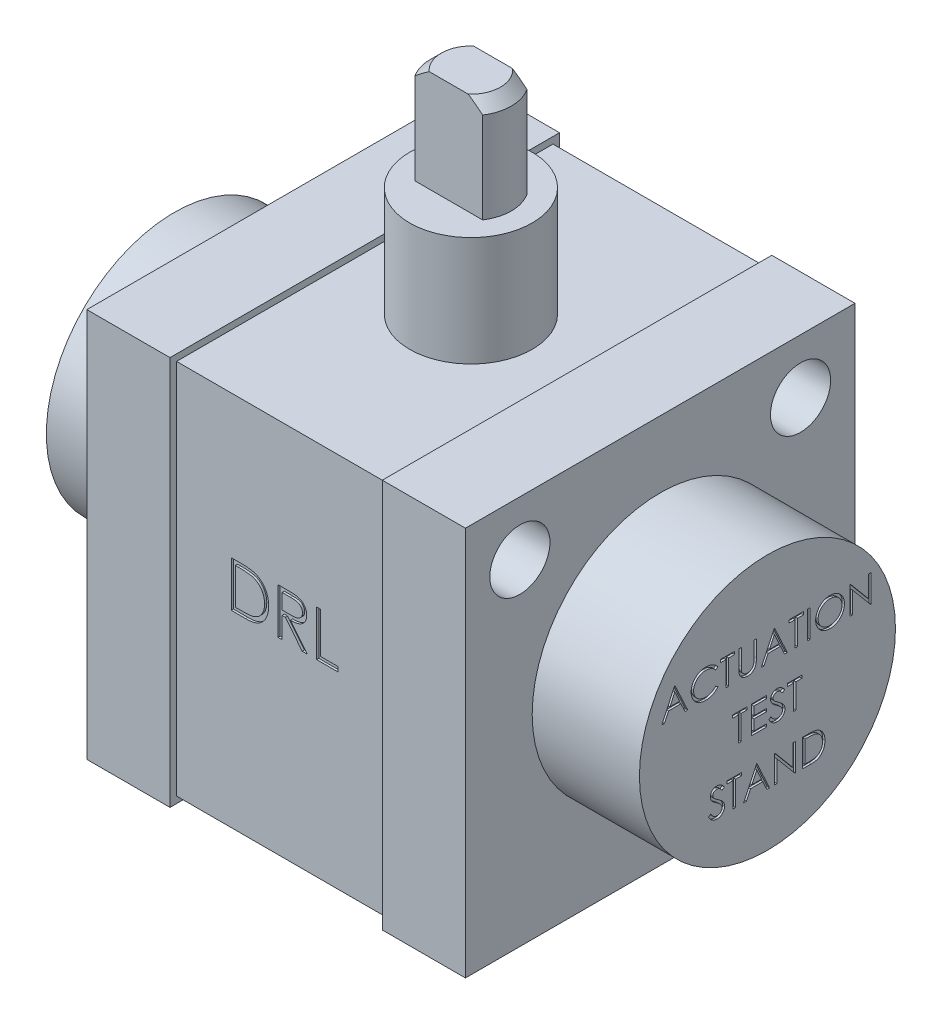
SolidWorks part; units mm, degrees
ref_plane "Front Plane" through (0, 0, 0) normal (0, 0, 1) x (1, 0, 0)
ref_plane "Top Plane" through (0, 0, 0) normal (0, 1, 0) x (1, 0, 0)
ref_plane "Right Plane" through (0, 0, 0) normal (1, 0, 0) x (0, 0, -1)
sketch "Sketch4" plane through (0, 0, 0) normal (1, 0, 0) x (0, 0, -1)
  line L0 (-21.844, 21.844) -> (21.844, 21.844)
  line L1 (-22.606, -22.606) -> (22.606, -22.606)
  line L2 (-22.606, -22.606) -> (-22.606, 22.606)
  line L3 (-22.606, 22.606) -> (22.606, 22.606)
  line L4 (22.606, -22.606) -> (22.606, 22.606)
  line L5 (-22.606, -22.606) -> (22.606, 22.606) construction
  line L6 (-22.606, 22.606) -> (22.606, -22.606) construction
  line L7 (21.844, -21.844) -> (21.844, 21.844)
  line L8 (-21.844, -21.844) -> (21.844, -21.844)
  line L9 (-21.844, -21.844) -> (-21.844, 21.844)
  point P0 (0, 0)
  dimension "D1" = 45.212
  dimension "D2" = 45.212
  dimension "D3" = 0.762
extrude "Boss-Extrude1" add sketch "Sketch4" against normal blind 9.652 contours L9 L8 L7 L0 | L1 L4 L3 L2 L8 L9 L0 L7 | L0 L7 L8 L9 | L2 L1 L4 L3 region at (0, 0, 0) region at (0, 0, 21.9666)
extrude "Boss-Extrude2" add sketch "Sketch4<3>" along normal blind 24.638 contours L9 L8 L7 L0 region at (0, 0, 0)
sketch "Sketch4<3>" plane through (0, 0, 0) normal (1, 0, 0) x (0, 0, -1) same geometry as "Sketch4"
extrude "Boss-Extrude3" add sketch "Sketch4<4>" along normal blind 9.652 from surface contours L9 L8 L7 L0 | L1 L4 L3 L2 L8 L9 L0 L7 region at (0, 0, 0) region at (0, 0, 21.9666) starting at face at (24.638, 0, 0)
sketch "Sketch4<4>" plane through (0, 0, 0) normal (1, 0, 0) x (0, 0, -1) same geometry as "Sketch4"
sketch "Sketch5" plane through (0, 21.844, 0) normal (0, 1, 0) x (1, 0, 0)
  line L0 (12.319, 21.844) -> (12.319, -21.844) construction
  line L1 (24.638, 21.844) -> (0, 21.844) construction
  line L2 (24.638, -21.844) -> (0, -21.844) construction
  circle A0 centre (12.319, 0) radius 7.112
  circle A1 centre (12.319, 0) radius 4.699
  dimension "D1" = 14.224
  dimension "D2" = 9.398
extrude "Boss-Extrude4" add sketch "Sketch5" along normal blind 12.7089 contours A0 L0 A1 | L0 A0 A1 | A1 L0 | L0 A1 | A1 | A0 region at (17.2355, 21.844, -4.9165) region at (12.16, 21.844, -5.9055) region at (14.3133, 21.844, 0) region at (10.3247, 21.844, 0)
extrude "Boss-Extrude5" add sketch "Sketch5<3>" along normal blind 11.811 from surface contours L0 A1 | A1 L0 region at (14.3133, 21.844, 0) region at (10.3247, 21.844, 0) starting at face at (12.319, 34.5529, 7.112)
sketch "Sketch5<3>" plane through (0, 21.844, 0) normal (0, 1, 0) x (1, 0, 0) same geometry as "Sketch5"
sketch "Sketch6" plane through (34.29, 0, 0) normal (1, 0, 0) x (0, 0, -1)
  line L0 (-22.606, 22.606) -> (-22.606, -22.606) construction
  line L1 (22.606, 22.606) -> (-22.606, 22.606) construction
  line L2 (0, 22.606) -> (0, -22.606) construction
  line L3 (22.606, -22.606) -> (-22.606, -22.606) construction
  circle A0 centre (-16.2865, 16.2865) radius 3.4925
  circle A1 centre (16.2865, 16.2865) radius 3.4925
  dimension "D3" = 6.985
  dimension "D1" = 6.3195
  dimension "D2" = 6.3195
extrude "Cut-Extrude1" cut sketch "Sketch6" against normal through all
sketch "Sketch7" plane through (34.29, 0, 0) normal (1, 0, 0) x (0, 0, -1)
  circle A0 centre (0, 0) radius 14.859
  dimension "D1" = 29.718
extrude "Boss-Extrude6" add sketch "Sketch7" along normal blind 12.446
extrude "Boss-Extrude7" add sketch "Sketch7<2>" against normal blind 12.446 from surface starting at face at (-9.652, 16.2865, 12.794)
sketch "Sketch7<2>" plane through (34.29, 0, 0) normal (1, 0, 0) x (0, 0, -1) same geometry as "Sketch7"
sketch "Sketch8" plane through (46.736, 0, 0) normal (1, 0, 0) x (0, 0, -1)
  line L0 (-14.3429, 3.8823) -> (14.3429, 3.8823) construction
  line L1 (0, 14.859) -> (0, -14.859) construction
  circle A0 centre (0, 0) radius 14.859 construction
  circle A1 centre (0, 0) radius 14.859 construction
  text T0 "ACTUATION\r\nTEST\r\nSTAND"
extrude "Cut-Extrude2" cut sketch "Sketch8" against normal blind 0.254
sketch "Sketch9" plane through (-22.098, 0, 0) normal (-1, 0, 0) x (0, 0, 1)
  line L0 (0, 14.859) -> (0, -14.859) construction
  line L1 (-13.8383, 5.4122) -> (13.8383, 5.4122) construction
  circle A1 centre (0, 0) radius 14.859
  circle A2 centre (0, 0) radius 14.859 construction
  text T0 "August \r\nRules\r\n"
  dimension "D1" = 0
extrude "Cut-Extrude3" cut sketch "Sketch9" against normal blind 0.254
sketch "Sketch10" plane through (0, 0, 21.844) normal (0, 0, 1) x (1, 0, 0)
  line L0 (0, 0) -> (24.638, 0) construction
  line L1 (24.638, 22.606) -> (24.638, -22.606) construction
  text T0 "DRL" font "Century Gothic" height in points 20
extrude "Cut-Extrude4" cut sketch "Sketch10" against normal blind 0.254
sketch "Sketch11" plane through (0, 0, -21.844) normal (0, 0, -1) x (-1, 0, 0)
  line L0 (0, 0) -> (-24.638, 0) construction
  line L1 (-24.638, -21.844) -> (-24.638, 21.844) construction
  text T0 "DRL" font "Century Gothic" height in points 20
extrude "Cut-Extrude5" cut sketch "Sketch11" against normal blind 0.254
sketch "Sketch12" plane through (0, 46.3639, 0) normal (0, 1, 0) x (1, 0, 0)
  line L0 (8.3862, 2.5717) -> (16.2518, 2.5717)
  line L1 (8.3862, -2.5718) -> (16.2518, -2.5718)
  arc A0 (8.3862, -2.5718) -> (16.2518, -2.5718) centre (12.319, 0) ccw
  circle A1 centre (12.319, 0) radius 4.699
  arc A2 (16.2518, 2.5717) -> (8.3862, 2.5717) centre (12.319, 0) ccw
  dimension "D2" = 5.1435
  dimension "D1" = 0
extrude "Cut-Extrude6" cut sketch "Sketch12" against normal up to surface (11.811 mm away) up to face at (12.319, 34.5529, 4.699)
chamfer "Chamfer1" distance 1.27 angle 45 2 edges at (7.62, 46.3639, 0) (17.018, 46.3639, 0)
